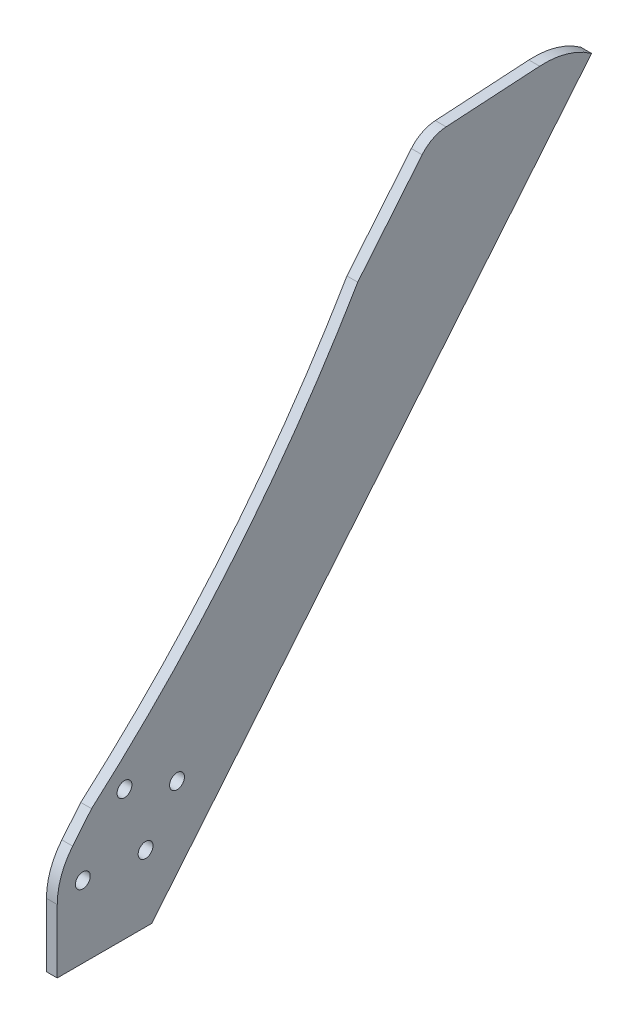
SolidWorks part; units mm, degrees
material "MS-Bis 80"
ref_plane "Front Plane" through (0, 0, 0) normal (0, 0, 1) x (1, 0, 0)
ref_plane "Top Plane" through (0, 0, 0) normal (0, 1, 0) x (1, 0, 0)
ref_plane "Right Plane" through (0, 0, 0) normal (1, 0, 0) x (0, 0, -1)
sketch "Sketch1" plane through (0, 0, 0) normal (1, 0, 0) x (0, 0, -1)
  line L0 (305.2186, 670.2186) -> (400.6303, 785.9623)
  line L1 (436.1591, 804.0652) -> (574.7501, 812.5417)
  line L2 (651.6621, 790.5294) -> (0, 0)
  line L3 (0, 0) -> (-140, 0)
  line L5 (-140, 0) -> (-140, 94.2216)
  line L6 (-117.1625, 157.8294) -> (-89.1137, 191.8552)
  line L7 (127.343, 415.135) -> (108.0524, 431.0369) construction
  line L8 (305.2186, 670.2186) -> (-89.1137, 191.8552) construction
  arc A0 (-140, 94.2216) -> (-117.1625, 157.8294) centre (-40, 94.2216) cw
  arc A1 (436.1591, 804.0652) -> (400.6303, 785.9623) centre (439.2116, 754.1584) ccw
  arc A2 (651.6621, 790.5294) -> (574.7501, 812.5417) centre (582.076, 692.7656) ccw
  arc A3 (-89.1137, 191.8552) -> (305.2186, 670.2186) centre (-1365.0929, 1645.4042) ccw
  point P16 (-140, 130.1253)
  dimension "D19" = 120
  dimension "D22" = 50
  dimension "D8" = 100
  dimension "D1" = 1024.5
  dimension "D3" = 129.5
  dimension "D4" = 130.1253
  dimension "D5" = 25
  dimension "D6" = 140
  dimension "D7" = 80
  dimension "D21" = 150
  dimension "D23" = 47
  dimension "D26" = 80
sheet metal parameters "Sheet-Metal1" thickness 16 parameters "D1"=92
base flange "Base-Flange1" sketch "Sketch1" thickness 16 reverse thickness direction no parameters "D1"=92
sketch "Sketch3" plane through (0, 0, 0) normal (1, 0, 0) x (0, 0, -1)
  line L1 (-140, 0) -> (0, 0) construction
  circle A0 centre (-40.3445, 192.5621) radius 11
  circle A1 centre (-102.0867, 106.4) radius 11
  circle A2 centre (-9.1, 98.8189) radius 11
  circle A3 centre (37.4979, 163.8469) radius 11
  dimension "D7" = 22
  dimension "D1" = 92.9867
  dimension "D2" = 7.5811
  dimension "D3" = 65.028
  dimension "D4" = 46.5979
  dimension "D5" = 28.7152
  dimension "D6" = 77.8424
  dimension "D8" = 9.1
  dimension "D9" = 106.4
extrude "Cut-Holes" cut sketch "Sketch3" against normal through all
flat pattern "Flat-Pattern1" [suppressed]
sketch "Bend-Lines1" plane through (0, 0, 0) normal (0, 1, 0) x (1, 0, 0)
sketch3d "Bounding-Box1" [suppressed]
  line L0 (1308.4495, -1714.1181, 0) -> (2016.755, -854.8748, 0) construction
  line L1 (1161.2256, -1592.7561, 0) -> (1869.5311, -733.5128, 0) construction
  line L2 (1308.4495, -1714.1181, 0) -> (1161.2256, -1592.7561, 0) construction
  line L3 (2016.755, -854.8748, 0) -> (1869.5311, -733.5128, 0) construction
